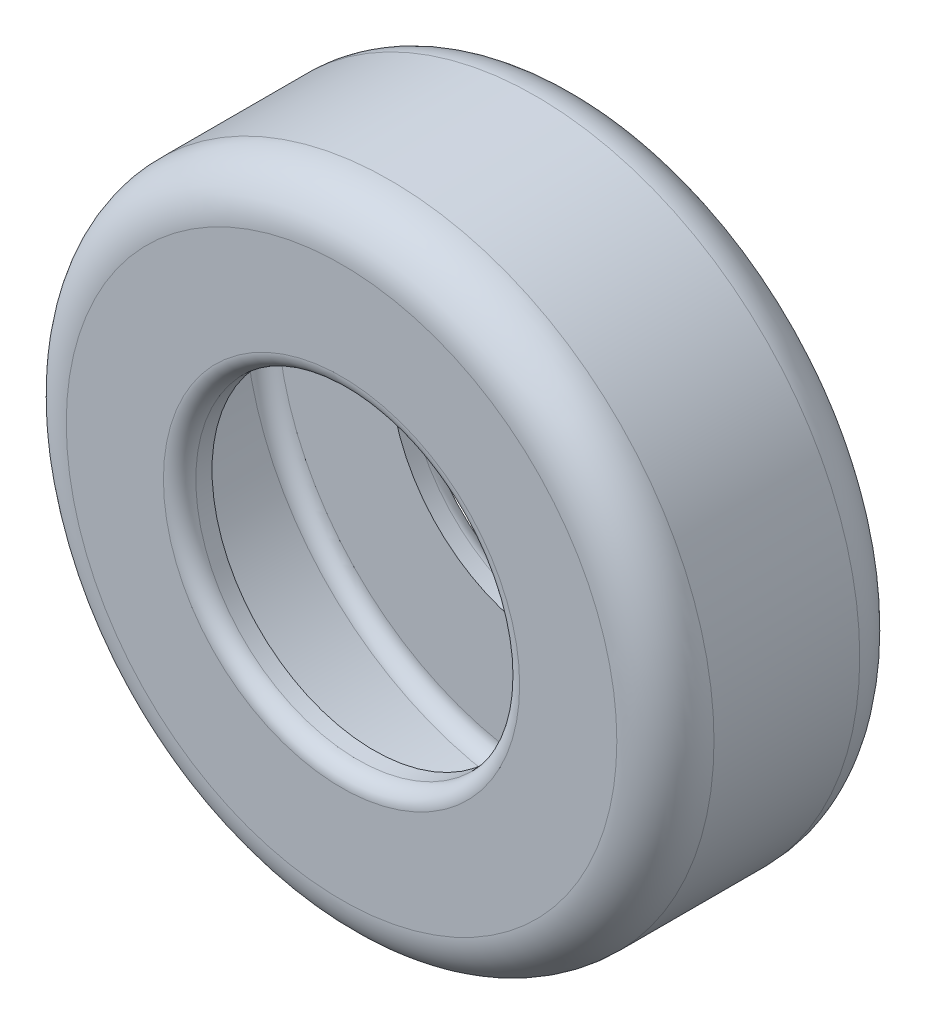
SolidWorks part; units mm, degrees
ref_plane "Front Plane" through (0, 0, 0) normal (0, 0, 1) x (1, 0, 0)
ref_plane "Top Plane" through (0, 0, 0) normal (0, 1, 0) x (1, 0, 0)
ref_plane "Right Plane" through (0, 0, 0) normal (1, 0, 0) x (0, 0, -1)
sketch "Sketch2" plane through (0, 0, 0) normal (0, 0, 1) x (1, 0, 0)
  circle A0 centre (0, 0) radius 10
  dimension "D1" = 20
extrude "Extrude-Thin1" add sketch "Sketch2" along normal blind 15 thin thin type one direction wall 10
fillet "Fillet1" radius 3 2 edges at (20, 0, 0) (20, 0, 15)
fillet "Fillet2" radius 1 2 edges at (10, 0, 0) (10, 0, 15)
shell "Shell1" thickness 2 removed face at (10, 0, 1)
